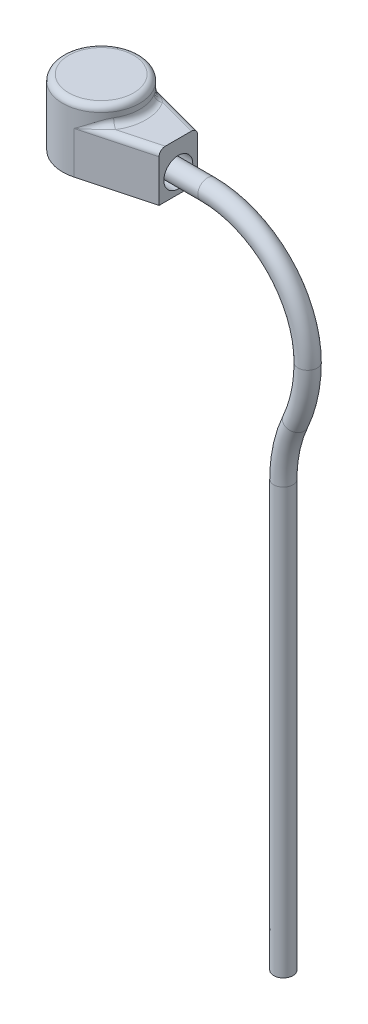
SolidWorks part; units mm, degrees
ref_plane "Front Plane" through (0, 0, 0) normal (0, 0, 1) x (1, 0, 0)
ref_plane "Top Plane" through (0, 0, 0) normal (0, 1, 0) x (1, 0, 0)
ref_plane "Right Plane" through (0, 0, 0) normal (1, 0, 0) x (0, 0, -1)
sketch "Sketch1" plane through (0, 0, 0) normal (0, 1, 0) x (1, 0, 0)
  circle A0 centre (0, 0) radius 4.572 construction
  circle A1 centre (0, 0) radius 6.35
  dimension "D1" = 9.144
  dimension "D2" = 12.7
extrude "Boss-Extrude1" add sketch "Sketch1" along normal blind 10.795
sketch "Sketch2" plane through (0, 0, 0) normal (0, -1, 0) x (1, 0, 0)
  circle A0 centre (0, 0) radius 4.572
  dimension "D1" = 9.144
extrude "Cut-Extrude1" cut sketch "Sketch2" against normal blind 10.414
chamfer "Chamfer1" distance 0.5 angle 45 1 edges at (0, 0, -4.572)
sketch "Sketch3" plane through (0, 0, 0) normal (0, -1, 0) x (1, 0, 0)
  line L0 (0, 0) -> (12.7, 0) construction
  line L1 (12.7, 0) -> (12.7, 3.175)
  line L2 (12.7, 3.175) -> (1.6415, 6.1342)
  line L3 (12.7, 0) -> (12.7, -3.175)
  line L4 (12.7, -3.175) -> (1.6415, -6.1342)
  circle A0 centre (0, 0) radius 6.35 construction
  arc A1 (1.6415, 6.1342) -> (1.6415, -6.1342) centre (0, 0) cw
  dimension "D1" = 6.35
  dimension "D2" = 12.7
extrude "Boss-Extrude2" add sketch "Sketch3" against normal blind 7.9375
sketch "Sketch4" plane through (12.7, 0, 0) normal (1, 0, 0) x (0, 0, -1)
  circle A0 centre (0, 3.175) radius 2.3813
  dimension "D1" = 4.7625
  dimension "D2" = 3.175
extrude "Cut-Extrude2" cut sketch "Sketch4" against normal blind 10.9375
fillet "Fillet1" radius 1 4 edges at (6.35, 7.9375, 0) (7.1707, 7.9375, 4.6546) (7.1707, 7.9375, -4.6546) (0, 10.795, 6.35)
ref_plane "Plane1" through (0, 0, 0) normal (0, 0, 1) x (1, 0, 0)
sketch "Sketch5" plane through (0, 0, 0) normal (0, 0, 1) x (1, 0, 0)
  line L0 (10, 3.175) -> (17.5, 3.175)
  line L3 (12.7, 0.7937) -> (12.7, 5.5563) construction
  line L4 (30, -31.9798) -> (30, -101.9798)
  arc A0 (17.5, 3.175) -> (34, -13.325) centre (17.5, -13.325) cw
  arc A1 (34, -13.325) -> (31.978, -22.7549) centre (11, -13.325) cw
  arc A2 (31.978, -22.7549) -> (30, -31.9798) centre (52.5, -31.9798) ccw
  dimension "D3" = 16.5
  dimension "D5" = 23
  dimension "D6" = 22.5
  dimension "D1" = 10
  dimension "D2" = 7.5
  dimension "D4" = 3.175
  dimension "D7" = 30
  dimension "D8" = 70
ref_plane "Plane2" through (30, -101.9798, 0) normal (0, -1, 0) x (-1, 0, 0)
sketch "Sketch6" plane through (30, -101.9798, 0) normal (0, -1, 0) x (-1, 0, 0)
  circle A0 centre (0, 0) radius 1.5875
  dimension "D1" = 3.175
sweep "Sweep1" add profiles "Sketch6" path "Sketch5"
